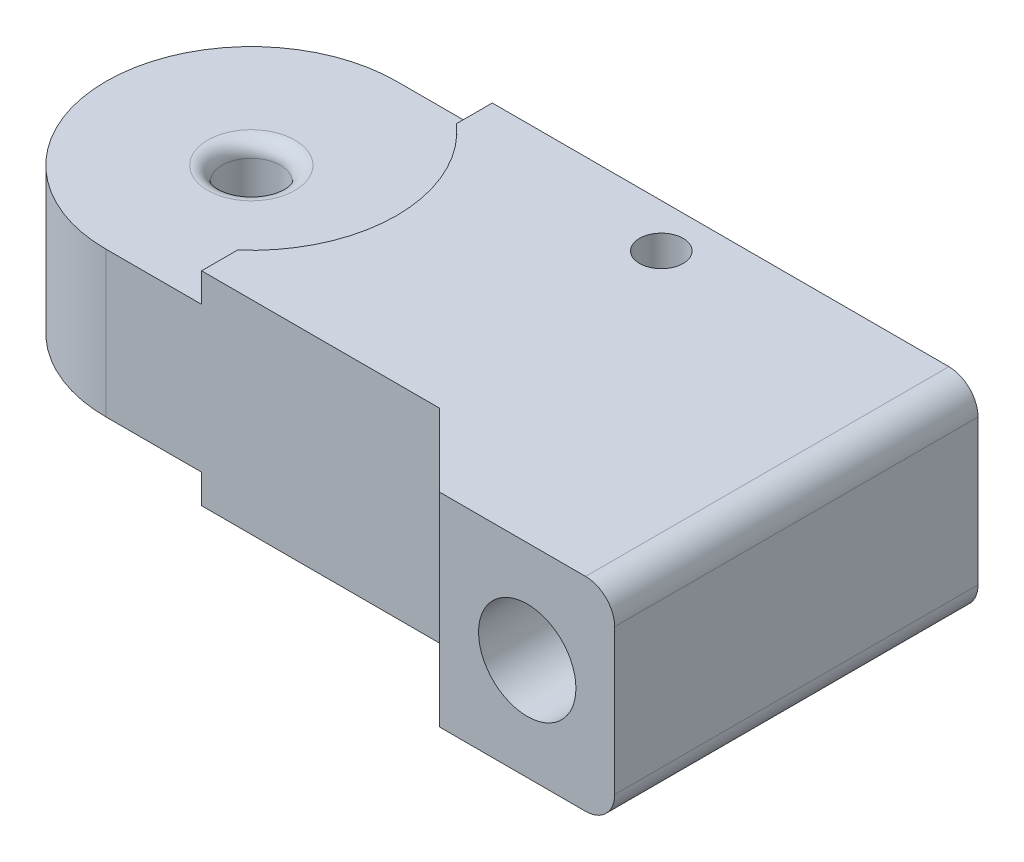
SolidWorks part; units mm, degrees
ref_plane "Front" through (0, 0, 0) normal (0, 0, 1) x (1, 0, 0)
ref_plane "Top" through (0, 0, 0) normal (0, 1, 0) x (1, 0, 0)
ref_plane "Right" through (0, 0, 0) normal (1, 0, 0) x (0, 0, -1)
sketch "Sketch1" plane through (0, 0, 0) normal (0, 1, 0) x (1, 0, 0)
  line L1 (25, -10) -> (-25, -10)
  line L2 (25, -10) -> (25, 10)
  line L3 (25, 10) -> (-25, 10)
  line L4 (-25, -10) -> (-25, 10)
  line L5 (25, -10) -> (-25, 10) construction
  line L6 (25, 10) -> (-25, -10) construction
  point P0 (0, 0)
  dimension "D1" = 50
  dimension "D2" = 20
extrude "Boss-Extrude1" add sketch "Sketch1" along normal blind 10
sketch "Sketch2" plane through (0, 10, 0) normal (0, 1, 0) x (1, 0, 0)
  circle A1 centre (-15, 0) radius 2
  dimension "D2" = 4
fillet "Fillet1" radius 10 2 edges at (-25, 5, 10) (-25, 5, -10)
extrude "Cut-Extrude1" cut sketch "Sketch2" against normal blind 10
sketch "Sketch4" plane through (0, 0, -10) normal (0, 0, -1) x (-1, 0, 0)
  circle A0 centre (-18.9842, 5) radius 3.35
  dimension "D1" = 6.7
extrude "Cut-Extrude2" cut sketch "Sketch4" against normal blind 40
sketch "Sketch6" plane through (0, 10, 0) normal (0, 1, 0) x (1, 0, 0)
  line L0 (-8.4202, 10) -> (-8.4202, 7.5304)
  line L1 (25, 10) -> (-8.4202, 10)
  line L2 (25, 10) -> (25, -10)
  line L3 (25, -10) -> (-8.4202, -10)
  line L5 (8.2899, -10) -> (8.2899, 10) construction
  line L6 (25, 0) -> (-15, 0) construction
  line L7 (-8.4202, -7.5304) -> (-8.4202, -10)
  arc A0 (-8.4202, -7.5304) -> (-8.4202, 7.5304) centre (-15, 0) ccw
  point P287 (8.2899, 0)
extrude "Boss-Extrude3" add sketch "Sketch6" along normal blind 2
sketch "Sketch7" plane through (0, 12, 0) normal (0, 1, 0) x (1, 0, 0)
  line L1 (25, 10) -> (-8.4202, 10) construction
  circle A0 centre (6.2102, 7) radius 1.5
  dimension "D1" = 3
  dimension "D2" = 3
extrude "Cut-Extrude3" cut sketch "Sketch7" against normal blind 20
ref_plane "Plane1" through (0, 5, 0) normal (0, -1, 0) x (-1, 0, 0)
mirror "Mirror3" about plane through (0, 5, 0) normal (0, -1, 0) of "Cut-Extrude3", "Boss-Extrude3"
fillet "Fillet3" radius 2 2 edges at (25, -2, 0) (25, 12, 0)
fillet "Fillet4" radius 1 2 edges at (-15, 10, 2) (-15, 0, 2)
sketch "Sketch8" plane through (0, 0, 10) normal (0, 0, 1) x (1, 0, 0)
  line L0 (12.9642, 12) -> (12.9642, -2)
  line L8 (-8.4202, -2) -> (23, -2)
  line L9 (25, 0) -> (25, 10)
  line L10 (23, 12) -> (-8.4202, 12)
  line L11 (-8.4202, 12) -> (-8.4202, 10)
  line L12 (-8.4202, 10) -> (-15, 10)
  line L13 (-15, 10) -> (-15, 0)
  line L14 (-15, 0) -> (-8.4202, 0)
  line L15 (-8.4202, 0) -> (-8.4202, -2)
  line L16 (12.9642, -2) -> (23, -2)
  line L17 (25, 0) -> (25, 10)
  line L18 (23, 12) -> (12.9642, 12)
  circle A0 centre (18.9842, 5) radius 3.35
  arc A2 (23, -2) -> (25, 0) centre (23, 0) ccw
  arc A3 (25, 10) -> (23, 12) centre (23, 10) ccw
  arc A4 (23, -2) -> (25, 0) centre (23, 0) ccw
  arc A5 (25, 10) -> (23, 12) centre (23, 10) ccw
  dimension "D2" = 6.02
  dimension "D1" = 0
extrude "Boss-Extrude4" add sketch "Sketch8" along normal blind 5
chamfer "Chamfer1" distance 5 angle 45 1 edges at (12.9642, 5, 10)
